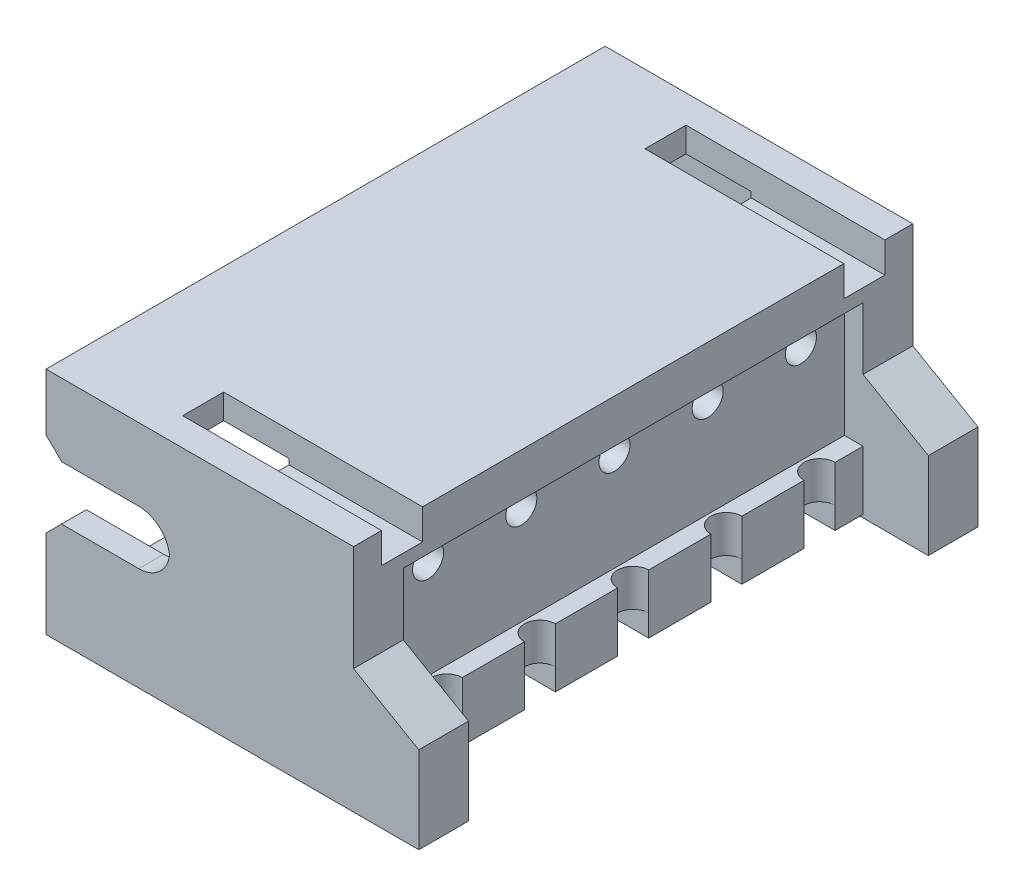
SolidWorks part; units mm, degrees
ref_plane "정면" through (0, 0, 0) normal (0, 0, 1) x (1, 0, 0)
ref_plane "윗면" through (0, 0, 0) normal (0, 1, 0) x (1, 0, 0)
ref_plane "우측면" through (0, 0, 0) normal (1, 0, 0) x (0, 0, -1)
sketch "스케치1" plane through (0, 0, 0) normal (0, 0, 1) x (1, 0, 0)
  line L1 (0, 0) -> (6, 0)
  line L2 (0, 0) -> (0, 3.7)
  line L3 (0, 3.7) -> (6, 3.7)
  line L4 (6, 0) -> (6, 3.7)
  dimension "D1" = 3.7
  dimension "D2" = 6
extrude "보스-돌출1" add sketch "스케치1" along normal blind 9
sketch "스케치2" plane through (0, 0, 9) normal (0, 0, 1) x (1, 0, 0)
  line L0 (0, 3.7) -> (0, 0) construction
  line L1 (6, 3.7) -> (4.95, 3.7)
  line L2 (6, 3.7) -> (6, 1.3938)
  line L3 (6, 1.3938) -> (4.95, 2)
  line L4 (4.95, 3.7) -> (4.95, 2)
  line L6 (1.9934, 2.1) -> (4.95, 2.1) construction
  line L7 (0, 2.535) -> (1.9934, 2.535)
  line L8 (0, 2.535) -> (0, 1.665)
  line L9 (0, 1.665) -> (1.9934, 1.665)
  line L10 (1.9934, 2.535) -> (1.9934, 1.665)
  line L12 (0, 0) -> (6, 0) construction
  dimension "D1" = 4.95
  dimension "D2" = 120
  dimension "D3" = 2
  dimension "D4" = 0.87
  dimension "D5" = 0.1
extrude "컷-돌출1" cut sketch "스케치2" against normal through all
chamfer "모따기1" distance 0.25 angle 45 2 edges at (0, 1.665, 4.5) (0, 2.535, 4.5)
fillet "필렛1" radius 0.5 2 edges at (1.9934, 1.665, 4.5) (1.9934, 2.535, 4.5)
sketch "스케치3" plane through (0, 0, 0) normal (-1, 0, 0) x (0, 0, 1)
  line L0 (9, 3.7) -> (0, 3.7) construction
  line L1 (0.4, 3.3) -> (8.6, 3.3)
  line L2 (0.4, 3.3) -> (0.4, 0.4)
  line L3 (0.4, 0.4) -> (8.6, 0.4)
  line L4 (8.6, 3.3) -> (8.6, 0.4)
  line L5 (0, 1.415) -> (0, 0) construction
  line L6 (9, 0) -> (0, 0) construction
  line L7 (9, 1.415) -> (9, 0) construction
  dimension "D1" = 0.4
  dimension "D2" = 0.4
  dimension "D3" = 0.4
  dimension "D4" = 0.4
extrude "컷-돌출2" cut sketch "스케치3" against normal blind 2.8
sketch "스케치4" plane through (6, 0, 0) normal (1, 0, 0) x (0, 0, -1)
  line L0 (0, 3.7) -> (-9, 3.7) construction
  line L1 (-8.2, 3) -> (-0.8, 3)
  line L2 (-8.2, 3) -> (-8.2, 0)
  line L3 (-8.2, 0) -> (-0.8, 0)
  line L4 (-0.8, 3) -> (-0.8, 0)
  line L5 (-9, 3.7) -> (-9, 2) construction
  line L6 (0, 3.7) -> (0, 2) construction
  line L7 (-9, 0) -> (0, 0) construction
  dimension "D1" = 0.7
  dimension "D2" = 0.8
  dimension "D3" = 0.8
extrude "컷-돌출3" cut sketch "스케치4" against normal up to surface (1.05 mm away) up to face at (4.95, 2.85, 4.5)
sketch "스케치5" plane through (4.95, 0, 0) normal (1, 0, 0) x (0, 0, -1)
  line L0 (-0.8, 0) -> (-0.8, 1.3938) construction
  line L1 (-8.2, 3) -> (-0.8, 3)
  line L2 (-8.2, 3) -> (-8.2, 1)
  line L3 (-8.2, 1) -> (-0.8, 1)
  line L4 (-0.8, 3) -> (-0.8, 1)
  line L5 (-8.2, 2) -> (-8.2, 0) construction
  line L6 (-8.2, 0) -> (-0.8, 0) construction
  line L7 (0, 3.7) -> (-9, 3.7) construction
  dimension "D1" = 1
  dimension "D2" = 0.7
extrude "컷-돌출4" cut sketch "스케치5" against normal blind 0.3
sketch "스케치6" plane through (0, 0, 0) normal (0, -1, 0) x (1, 0, 0)
  line L0 (4.95, 8.2) -> (4.95, 0.8) construction
  circle A0 centre (4.95, 4.5) radius 0.25
  circle A1 centre (4.95, 6) radius 0.25
  circle A2 centre (4.95, 3) radius 0.25
  circle A3 centre (4.95, 7.5) radius 0.25
  circle A4 centre (4.95, 1.5) radius 0.25
  dimension "D5" = 0.5
  dimension "D1" = 6
  dimension "D2" = 1.5
  dimension "D3" = 1.5
  dimension "D4" = 1.5
extrude "컷-돌출5" cut sketch "스케치6" against normal up to surface (1 mm away) up to face at (4.8, 1, 4.5)
sketch "스케치7" plane through (4.65, 0, 0) normal (1, 0, 0) x (0, 0, -1)
  line L0 (-7.5, 1) -> (-7.5, 2.6) construction
  line L1 (-7.25, 1) -> (-7.75, 1) construction
  line L2 (-7.5, 2.6) -> (-1.5, 2.6) construction
  line L3 (-1.5, 2.6) -> (-1.5, 1) construction
  line L4 (-1.25, 1) -> (-1.75, 1) construction
  line L5 (-6, 1) -> (-6, 2.6) construction
  line L6 (-5.75, 1) -> (-6.25, 1) construction
  line L7 (-4.5, 1) -> (-4.5, 2.6) construction
  line L8 (-8.2, 1) -> (-0.8, 1) construction
  line L9 (-3, 1) -> (-3, 2.6) construction
  line L10 (-2.75, 1) -> (-3.25, 1) construction
  line L11 (-0.8, 3) -> (-8.2, 3) construction
  circle A0 centre (-7.5, 2.6) radius 0.25
  circle A1 centre (-6, 2.6) radius 0.25
  circle A2 centre (-4.5, 2.6) radius 0.25
  circle A3 centre (-3, 2.6) radius 0.25
  circle A4 centre (-1.5, 2.6) radius 0.25
  dimension "D2" = 0.5
  dimension "D1" = 0.4
extrude "컷-돌출6" cut sketch "스케치7" against normal through all
sketch "스케치8" plane through (0, 0, 0) normal (0, -1, 0) x (1, 0, 0)
  line L0 (4.95, 2.75) -> (4.95, 1.75) construction
  line L1 (4.95, 7.75) -> (3.95, 7.75)
  line L2 (4.95, 7.75) -> (4.95, 7.25)
  line L3 (4.95, 7.25) -> (3.95, 7.25)
  line L4 (3.95, 7.75) -> (3.95, 7.25)
  line L5 (4.95, 6.25) -> (3.95, 6.25)
  line L6 (4.95, 6.25) -> (4.95, 5.75)
  line L7 (4.95, 5.75) -> (3.95, 5.75)
  line L8 (3.95, 6.25) -> (3.95, 5.75)
  line L9 (4.95, 4.75) -> (3.95, 4.75)
  line L10 (4.95, 4.75) -> (4.95, 4.25)
  line L11 (4.95, 4.25) -> (3.95, 4.25)
  line L12 (3.95, 4.75) -> (3.95, 4.25)
  line L13 (4.95, 3.25) -> (3.95, 3.25)
  line L14 (4.95, 3.25) -> (4.95, 2.75)
  line L15 (4.95, 2.75) -> (3.95, 2.75)
  line L16 (3.95, 3.25) -> (3.95, 2.75)
  line L17 (4.95, 1.75) -> (3.95, 1.75)
  line L18 (4.95, 1.75) -> (4.95, 1.25)
  line L19 (4.95, 1.25) -> (3.95, 1.25)
  line L20 (3.95, 1.75) -> (3.95, 1.25)
  line L21 (4.95, 5.75) -> (4.95, 4.75) construction
  line L22 (4.95, 7.25) -> (4.95, 6.25) construction
  arc A0 (4.95, 3.25) -> (4.95, 2.75) centre (4.95, 3) ccw construction
  point P25 (4.95, 1.25)
  point P27 (4.95, 2.75)
  point P33 (4.95, 4.25)
  point P35 (4.95, 5.75)
  point P38 (4.95, 7.25)
  dimension "D1" = 1
extrude "컷-돌출7" cut sketch "스케치8" against normal up to surface (0.4 mm away) up to face at (1.4, 0.4, 4.5)
sketch "스케치9" plane through (0, 0, 0) normal (0, -1, 0) x (1, 0, 0)
  line L0 (0, 9) -> (0, 0) construction
  line L1 (0, 8.2) -> (4.95, 8.2)
  line L2 (0, 8.2) -> (0, 4.85)
  line L3 (0, 4.85) -> (3.95, 4.85)
  line L4 (4.95, 8.2) -> (4.95, 4.85)
  line L5 (4.95, 0.8) -> (6, 0.8) construction
  line L6 (0, 0.8) -> (4.95, 0.8)
  line L7 (0, 0.8) -> (0, 4.15)
  line L8 (0, 4.15) -> (3.95, 4.15)
  line L9 (4.95, 0.8) -> (4.95, 4.15)
  line L10 (4.95, 8.2) -> (6, 8.2) construction
  line L11 (4.95, 7.25) -> (4.95, 6.25) construction
  line L12 (4.95, 2.75) -> (4.95, 1.75) construction
  line L13 (3.95, 4.85) -> (3.95, 4.15)
  line L14 (4.95, 4.5) -> (3.95, 4.5) construction
  line L16 (3.95, 4.75) -> (3.95, 4.25) construction
  line L17 (4.95, 0.8) -> (4.95, 8.2) construction
  point P22 (4.8681, 4.5096)
  point P23 (4.95, 4.5)
  dimension "D1" = 0.7
extrude "컷-돌출8" cut sketch "스케치9" against normal blind 0.05 and the other way through all
sketch "스케치10" plane through (4.95, 0, 0) normal (1, 0, 0) x (0, 0, -1)
  line L0 (0, 3.7) -> (-9, 3.7) construction
  line L1 (-8.55, 3.7) -> (-7.89, 3.7)
  line L2 (-8.55, 3.7) -> (-8.55, 3.21)
  line L3 (-8.55, 3.21) -> (-7.89, 3.21)
  line L4 (-7.89, 3.7) -> (-7.89, 3.21)
  line L5 (-9, 3.7) -> (-9, 2) construction
  line L6 (-0.45, 3.7) -> (-1.11, 3.7)
  line L7 (-0.45, 3.7) -> (-0.45, 3.21)
  line L8 (-0.45, 3.21) -> (-1.11, 3.21)
  line L9 (-1.11, 3.7) -> (-1.11, 3.21)
  line L10 (0, 3.7) -> (0, 2) construction
  point P10 (-8.55, 3.455)
  dimension "D1" = 0.45
  dimension "D2" = 0.45
  dimension "D3" = 0.66
  dimension "D4" = 0.49
extrude "컷-돌출9" cut sketch "스케치10" against normal blind 3.2
sketch "스케치11" plane through (2.8, 0, 0) normal (-1, 0, 0) x (0, 0, 1)
  line L0 (8.6, 0.4) -> (8.6, 3.3) construction
  line L1 (0.4, 0.4) -> (8.6, 0.4)
  line L2 (0.4, 0.4) -> (0.4, 1.9)
  line L3 (0.4, 1.9) -> (8.6, 1.9)
  line L4 (8.6, 0.4) -> (8.6, 1.9)
  dimension "D1" = 1.5
extrude "컷-돌출10" cut sketch "스케치11" against normal blind 0.25
sketch "스케치12" plane through (3.05, 0, 0) normal (-1, 0, 0) x (0, 0, 1)
  line L0 (8.6, 1.9) -> (0.4, 1.9) construction
  line L1 (3.75, 1.9) -> (5.25, 1.9)
  line L2 (3.75, 1.9) -> (3.75, 0.4)
  line L3 (3.75, 0.4) -> (5.25, 0.4)
  line L4 (5.25, 1.9) -> (5.25, 0.4)
  line L5 (0.4, 0.4) -> (8.6, 0.4) construction
  line L6 (8.6, 1.9) -> (0.4, 1.9) construction
  point P8 (4.5, 1.9)
  point P11 (4.5, 1.9)
  dimension "D1" = 1.5
extrude "컷-돌출11" cut sketch "스케치12" against normal blind 0.05
chamfer "모따기2" distance 0.3 angle 45 1 edges at (2.8, 1.9, 4.5)
